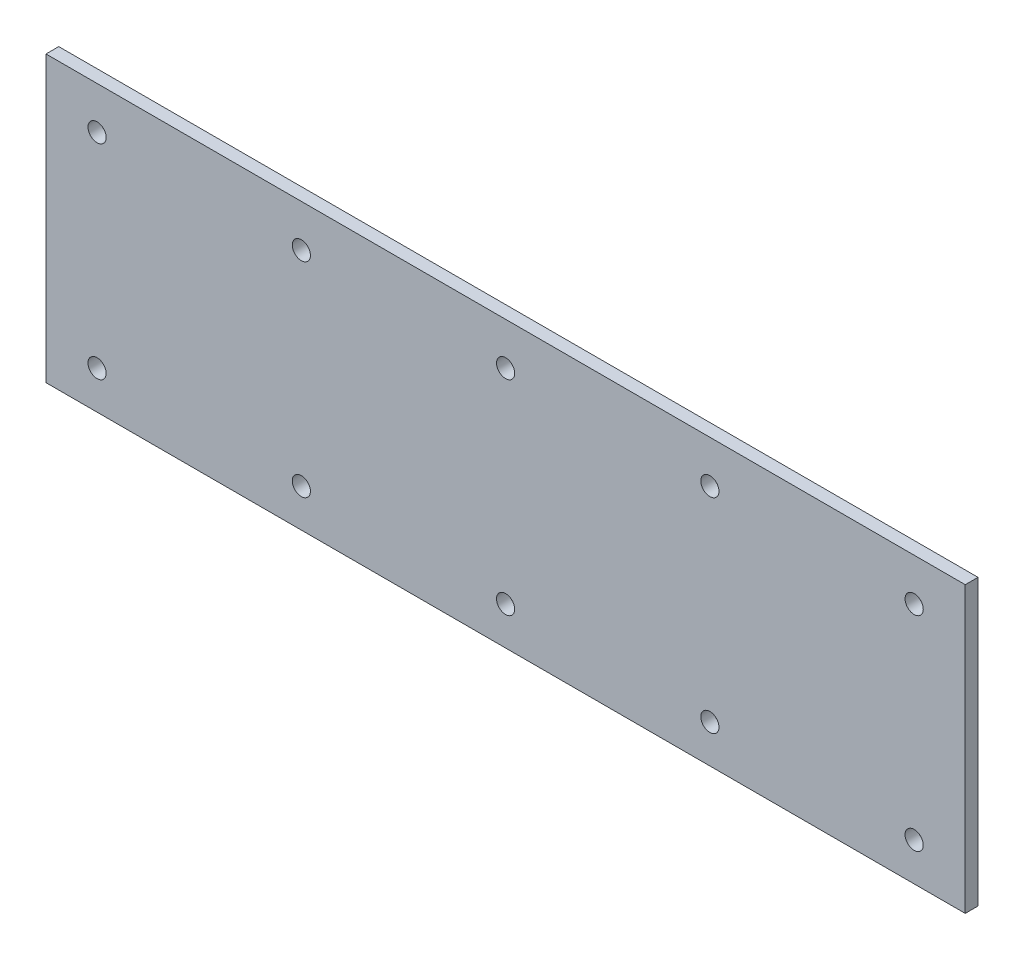
SolidWorks part; units mm, degrees
ref_plane "Front Plane" through (0, 0, 0) normal (0, 0, 1) x (1, 0, 0)
ref_plane "Top Plane" through (0, 0, 0) normal (0, 1, 0) x (1, 0, 0)
ref_plane "Right Plane" through (0, 0, 0) normal (1, 0, 0) x (0, 0, -1)
sketch "Sketch1" plane through (0, 0, 0) normal (0, 0, 1) x (1, 0, 0)
  line L1 (-57.15, 17.7) -> (57.15, 17.7)
  line L2 (-57.15, 17.7) -> (-57.15, -17.7)
  line L3 (-57.15, -17.7) -> (57.15, -17.7)
  line L4 (57.15, 17.7) -> (57.15, -17.7)
  point P4 (0, 17.7)
  point P6 (-57.15, 0)
  dimension "D1" = 114.3
  dimension "D2" = 35.4
extrude "Boss-Extrude1" add sketch "Sketch1" along normal blind 1.5875
hole_wizard "#4-40 Tapped Hole1" positions "3DSketch1" profile "Sketch2" tap size "#4-40" standard "ANSI Inch" end condition through all
sketch3d "3DSketch1"
  line L1 (-57.15, -17.7, 0) -> (57.15, -17.7, 0) construction
  line L3 (-57.15, 17.7, 1.5875) -> (-57.15, -17.7, 1.5875) construction
  point P0 (-50.8, 12.4413, 1.5875)
  point P2 (-50.8, -12.9587, 1.5875)
  dimension "D2" = 5
  dimension "D1" = 25.4
  dimension "D3" = 6.35
sketch "Sketch2" plane through (-50.8, 12.4413, 1.5875) normal (1, 0, 0) x (0, -1, 0)
  line L0 (0, 0) -> (0, 1.5875)
  line L1 (0, 1.5875) -> (1.1303, 1.5875)
  line L2 (1.1303, 1.5875) -> (1.1303, 0)
  line L5 (1.1303, 0) -> (0, 0)
  line L11 (0, -6.35) -> (0, 107.95) construction
  dimension "Thru Tap Drill Dia." = 2.2606
  dimension "Thru Tap Drill Depth" = 1.5875
cosmetic thread "Hole Thread1"
cosmetic thread "Hole Thread2"
pattern_linear "LPattern1" count 5 spacing 25.4 along (1, 0, 0) of "#4-40 Tapped Hole1"
cosmetic thread "Hole Thread3"
cosmetic thread "Hole Thread4"
cosmetic thread "Hole Thread5"
cosmetic thread "Hole Thread6"
cosmetic thread "Hole Thread7"
cosmetic thread "Hole Thread8"
cosmetic thread "Hole Thread9"
cosmetic thread "Hole Thread10"
equation "\"plate_height\"=35.4"
equation "\"D2@Sketch1\"=\"plate_height\""
equation "\"D2@3DSketch1\"=(\"plate_height\"-\"D1@3DSketch1\")/2"
